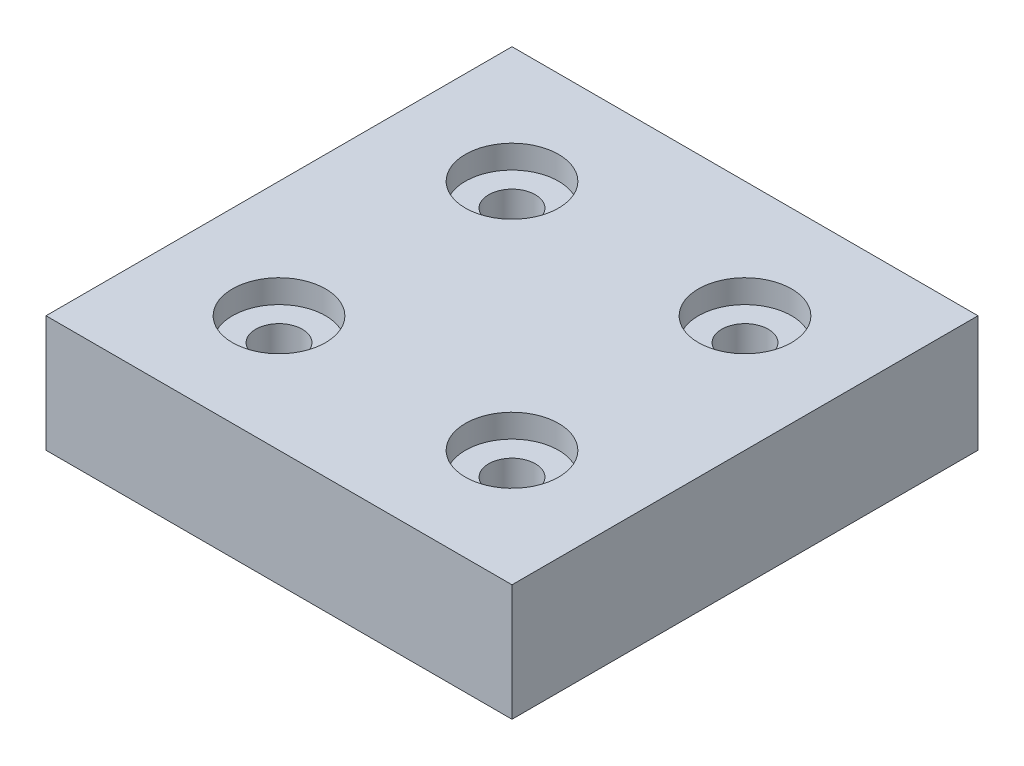
SolidWorks part; units mm, degrees
ref_plane "Front Plane" through (0, 0, 0) normal (0, 0, 1) x (1, 0, 0)
ref_plane "Top Plane" through (0, 0, 0) normal (0, 1, 0) x (1, 0, 0)
ref_plane "Right Plane" through (0, 0, 0) normal (1, 0, 0) x (0, 0, -1)
sketch "Sketch1" plane through (0, 0, 0) normal (0, 1, 0) x (1, 0, 0)
  line L1 (0, 0) -> (40, 0)
  line L2 (0, 0) -> (0, 40)
  line L3 (0, 40) -> (40, 40)
  line L4 (40, 0) -> (40, 40)
  circle A0 centre (10, 30) radius 2
  circle A1 centre (30, 30) radius 2
  circle A2 centre (30, 10) radius 2
  circle A3 centre (10, 10) radius 2
  dimension "D11" = 4
  dimension "D12" = 4
  dimension "D13" = 4
  dimension "D14" = 4
  dimension "D1" = 40
  dimension "D2" = 40
  dimension "D3" = 10
  dimension "D4" = 10
  dimension "D5" = 10
  dimension "D6" = 10
  dimension "D7" = 10
  dimension "D8" = 10
  dimension "D9" = 10
  dimension "D10" = 10
extrude "Boss-Extrude1" add sketch "Sketch1" along normal blind 10
sketch "Sketch2" plane through (0, 10, 0) normal (0, 1, 0) x (1, 0, 0)
  circle A40 centre (10, 10) radius 4
  circle A41 centre (10, 10) radius 4
  circle A43 centre (10, 30) radius 4
  circle A44 centre (10, 30) radius 4
  circle A46 centre (30, 30) radius 4
  circle A47 centre (30, 30) radius 4
  circle A49 centre (30, 10) radius 4
  circle A50 centre (30, 10) radius 4
  dimension "D1" = 2
  dimension "D2" = 2
  dimension "D3" = 2
  dimension "D4" = 2
extrude "Cut-Extrude1" cut sketch "Sketch2" against normal blind 2
equation "\"hSpacing\"=10"
equation "\"D3@Sketch1\"=\"hSpacing\""
equation "\"D5@Sketch1\"=\"hSpacing\""
equation "\"D6@Sketch1\"=\"hSpacing\""
equation "\"D4@Sketch1\"=\"hSpacing\""
equation "\"D7@Sketch1\"=\"hSpacing\""
equation "\"D8@Sketch1\"=\"hSpacing\""
equation "\"D9@Sketch1\"=\"hSpacing\""
equation "\"D10@Sketch1\"=\"hSpacing\""
equation "\"hDiam\"=4"
equation "\"D11@Sketch1\"=\"hDiam\""
equation "\"D12@Sketch1\"=\"hDiam\""
equation "\"D13@Sketch1\"=\"hDiam\""
equation "\"D14@Sketch1\"=\"hDiam\""
